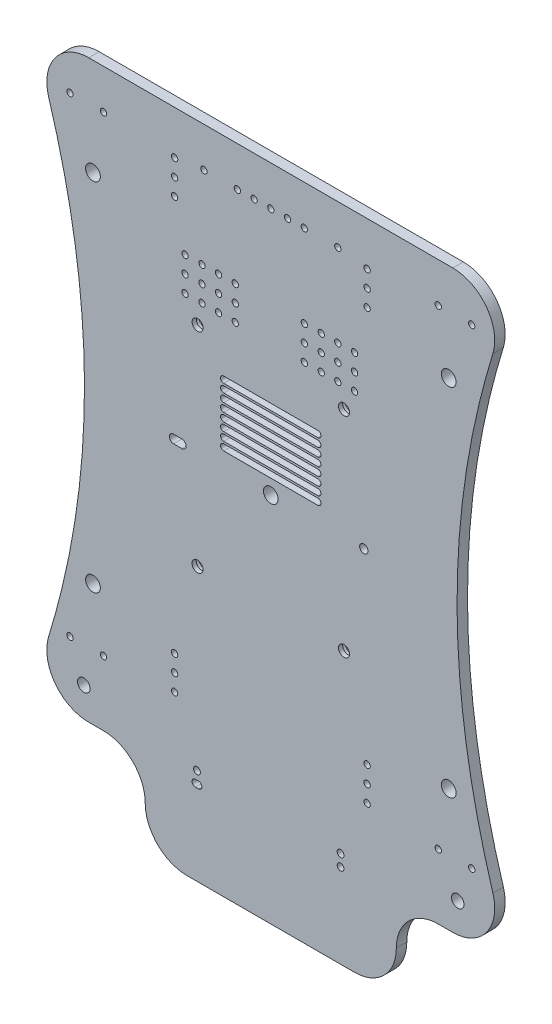
SolidWorks part; units mm, degrees
material "尼龙 101"
ref_plane "前视基准面" through (0, 0, 0) normal (0, 0, 1) x (1, 0, 0)
ref_plane "上视基准面" through (0, 0, 0) normal (0, 1, 0) x (1, 0, 0)
ref_plane "右视基准面" through (0, 0, 0) normal (1, 0, 0) x (0, 0, -1)
other "质心 (COM)"
sketch "草图1" plane through (0, 0, 0) normal (0, 0, 1) x (1, 0, 0)
  line L1 (219.5668, -321.513) -> (-113.5668, -321.513)
  line L2 (219.5668, -321.513) -> (219.5668, 86.513)
  line L3 (219.5668, 86.513) -> (-113.5668, 86.513)
  line L4 (-113.5668, -321.513) -> (-113.5668, 86.513)
  line L5 (53, 86.513) -> (53, -321.513) construction
  line L6 (219.5668, -117.5) -> (-113.5668, -117.5) construction
  point P0 (53, -117.5)
extrude "凸台-拉伸1" add sketch "草图1" along normal blind 5
sketch "草图2" plane through (0, 0, 0) normal (0, 0, -1) x (-1, 0, 0)
  line L0 (-16.9368, -260.7382) -> (-18.4087, -260.7382) construction
  line L1 (-16.9368, -262.3514) -> (-18.4087, -262.3514)
  line L2 (-16.9368, -259.125) -> (-18.4087, -259.125)
  line L3 (-6.5227, -123.5) -> (-10.4914, -123.5) construction
  line L4 (-6.5227, -125.5059) -> (-10.4914, -125.5059)
  line L5 (-6.5227, -121.4941) -> (-10.4914, -121.4941)
  circle A0 centre (-148.989, -4.9924) radius 1.5134
  circle A1 centre (-133, -5) radius 1.5134
  circle A2 centre (26.9975, -4.9986) radius 1.5134
  circle A3 centre (42.9864, -5.0062) radius 1.5134
  circle A4 centre (-149, -230) radius 1.5134
  circle A5 centre (-133, -230) radius 1.5134
  circle A6 centre (27, -230) radius 1.5134
  circle A7 centre (42.9864, -230) radius 1.5134
  circle A8 centre (-99, -212) radius 1.5134
  circle A9 centre (-99, -220) radius 1.5134
  circle A10 centre (-99, -228) radius 1.5134
  circle A11 centre (-7, -228) radius 1.5134
  circle A12 centre (-7, -212) radius 1.5134
  circle A13 centre (-7, -220) radius 1.5134
  circle A16 centre (-99, -6.872) radius 1.5134
  circle A17 centre (-99, -14.872) radius 1.5134
  circle A18 centre (-99, -22.872) radius 1.5134
  circle A19 centre (-7, -22.872) radius 1.5134
  circle A20 centre (-7, -6.872) radius 1.5134
  circle A21 centre (-7, -14.872) radius 1.5134
  circle A44 centre (-36, -60.5) radius 1.5134
  circle A45 centre (-12, -44.5) radius 1.5134
  circle A46 centre (-77.0909, -52.5) radius 1.5134
  circle A47 centre (-69, -60.5) radius 1.5134
  circle A48 centre (-93, -44.5) radius 1.5134
  circle A49 centre (-36, -44.5) radius 1.5134
  circle A50 centre (-93, -60.5) radius 1.5134
  circle A51 centre (-20.0909, -44.5) radius 1.5134
  circle A52 centre (-12, -60.5) radius 1.5134
  circle A53 centre (-28, -52.5) radius 1.5134
  circle A54 centre (-69, -44.5) radius 1.5134
  circle A55 centre (-85, -60.5) radius 1.5134
  circle A56 centre (-36, -52.5) radius 1.5134
  circle A57 centre (-20.0909, -52.5) radius 1.5134
  circle A58 centre (-69, -52.5) radius 1.5134
  circle A59 centre (-93, -52.5) radius 1.5134
  circle A60 centre (-85, -44.5) radius 1.5134
  circle A61 centre (-12, -52.5) radius 1.5134
  circle A62 centre (-28, -44.5) radius 1.5134
  circle A63 centre (-20.0909, -60.5) radius 1.5134
  circle A64 centre (-77.0909, -44.5) radius 1.5134
  circle A65 centre (-28, -60.5) radius 1.5134
  circle A66 centre (-85, -52.5) radius 1.5134
  circle A67 centre (-77.0909, -60.5) radius 1.5134
  circle A68 centre (-85, -5) radius 1.5134
  circle A69 centre (-69, -5) radius 1.5134
  circle A70 centre (-61, -5) radius 1.5134
  circle A71 centre (-53, -5) radius 1.5134
  circle A72 centre (-45, -5) radius 1.5134
  circle A73 centre (-37, -5) radius 1.5134
  circle A74 centre (-21, -5) radius 1.5134
  circle A75 centre (32.0139, -32.4785) radius 3.5256
  circle A76 centre (-138, -32.5) radius 3.5256
  circle A77 centre (32.0139, -202.6407) radius 3.5256
  circle A78 centre (-138, -202.5) radius 3.5256
  circle A79 centre (-17.9993, -70.5429) radius 2.6429
  circle A80 centre (-87.9571, -70.5) radius 2.6429
  circle A81 centre (-87.9571, -170.5) radius 2.6429
  circle A82 centre (-17.9571, -170.5) radius 2.6429
  circle A83 centre (-52.9571, -123.5) radius 3.5
  circle A84 centre (-86.322, -255.1502) radius 1.6383
  circle A85 centre (-86.322, -260.7382) radius 1.6066
  circle A86 centre (-17.6728, -255.1502) radius 1.6383
  arc A91 (-16.9368, -262.3514) -> (-16.9368, -259.125) centre (-16.9368, -260.7382) ccw
  arc A92 (-18.4087, -259.125) -> (-18.4087, -262.3514) centre (-18.4087, -260.7382) ccw
  circle A93 centre (-52.9571, -123.5) radius 44.45 construction
  circle A95 centre (-97.4071, -123.5) radius 1.9844
  arc A96 (-6.5227, -125.5059) -> (-6.5227, -121.4941) centre (-6.5227, -123.5) ccw
  arc A97 (-10.4914, -121.4941) -> (-10.4914, -125.5059) centre (-10.4914, -123.5) ccw
  point P70 (-17.6728, -260.7382)
  point P80 (-8.5071, -123.5)
extrude "切除-拉伸1" cut sketch "草图2" against normal through all
sketch "草图3" plane through (0, 0, 0) normal (0, 0, -1) x (-1, 0, 0)
  circle A0 centre (-17.9571, -170.5) radius 5
  circle A1 centre (-87.9571, -170.5) radius 5
  circle A2 centre (-17.9993, -70.5429) radius 5
  circle A3 centre (-87.9571, -70.5429) radius 5
extrude "切除-拉伸2" cut sketch "草图3" against normal blind 3
sketch "草图4" plane through (0, 0, 5) normal (0, 0, 1) x (1, 0, 0)
  line L9 (167.9571, -261) -> (112.9571, -261)
  line L10 (112.9571, -261) -> (112.9571, -301)
  line L11 (112.9571, -301) -> (-7.0429, -301)
  line L12 (-7.0429, -301) -> (-7.0429, -261)
  line L13 (-7.0429, -261) -> (-62.0429, -261)
  line L16 (-62.0429, 14) -> (167.9571, 14)
  line L18 (167.9571, -261) -> (-62.0429, 14) construction
  line L19 (-62.0429, -261) -> (167.9571, 14) construction
  line L20 (52.9571, 14) -> (52.9571, -301) construction
  spline S0 degree 2 poles (167.9571, -261) (116.0066, -123.3546) (167.9571, 14) knots 0 0 0 1 1 1
  spline S1 degree 2 poles (-62.0429, -261) (-10.0925, -123.3546) (-62.0429, 14) knots 0 0 0 1 1 1
  dimension "D1" = 55
  dimension "D2" = 120
  dimension "D3" = 40
  dimension "D4" = 275
extrude "切除-拉伸3" cut sketch "草图4" against normal through all flip side to cut
fillet "圆角1" radius 20 4 edges at (167.9571, 14, 2.5) (-62.0429, 14, 2.5) (-62.0429, -261, 2.5) (167.9571, -261, 2.5)
fillet "圆角2" radius 20 4 edges at (-7.0429, -301, 2.5) (112.9571, -301, 2.5) (-7.0429, -261, 2.5) (112.9571, -261, 2.5)
sketch "草图5" plane through (0, 0, 0) normal (0, 0, -1) x (-1, 0, 0)
  line L0 (-52.9571, -123.5) -> (-52.9571, -48.5) construction
  line L1 (-75.4571, -114.9826) -> (-30.4571, -114.9826) construction
  line L2 (-75.4571, -113.4826) -> (-30.4571, -113.4826)
  line L3 (-75.4571, -116.4826) -> (-30.4571, -116.4826)
  line L4 (-75.4571, -110.9826) -> (-30.4571, -110.9826) construction
  line L5 (-75.4571, -109.4826) -> (-30.4571, -109.4826)
  line L6 (-75.4571, -112.4826) -> (-30.4571, -112.4826)
  line L7 (-75.4571, -106.9826) -> (-30.4571, -106.9826) construction
  line L8 (-75.4571, -105.4826) -> (-30.4571, -105.4826)
  line L9 (-75.4571, -108.4826) -> (-30.4571, -108.4826)
  line L10 (-75.4571, -102.9826) -> (-30.4571, -102.9826) construction
  line L11 (-75.4571, -101.4826) -> (-30.4571, -101.4826)
  line L12 (-75.4571, -104.4826) -> (-30.4571, -104.4826)
  line L13 (-75.4571, -98.9826) -> (-30.4571, -98.9826) construction
  line L14 (-75.4571, -97.4826) -> (-30.4571, -97.4826)
  line L15 (-75.4571, -100.4826) -> (-30.4571, -100.4826)
  line L16 (-75.4571, -94.9826) -> (-30.4571, -94.9826) construction
  line L17 (-75.4571, -93.4826) -> (-30.4571, -93.4826)
  line L18 (-75.4571, -96.4826) -> (-30.4571, -96.4826)
  line L19 (-75.4571, -90.9826) -> (-30.4571, -90.9826) construction
  line L20 (-75.4571, -89.4826) -> (-30.4571, -89.4826)
  line L21 (-75.4571, -92.4826) -> (-30.4571, -92.4826)
  line L22 (-75.4571, -86.9826) -> (-30.4571, -86.9826) construction
  line L23 (-75.4571, -85.4826) -> (-30.4571, -85.4826)
  line L24 (-75.4571, -88.4826) -> (-30.4571, -88.4826)
  arc A0 (-75.4571, -113.4826) -> (-75.4571, -116.4826) centre (-75.4571, -114.9826) ccw
  arc A1 (-30.4571, -116.4826) -> (-30.4571, -113.4826) centre (-30.4571, -114.9826) ccw
  arc A2 (-75.4571, -109.4826) -> (-75.4571, -112.4826) centre (-75.4571, -110.9826) ccw
  arc A3 (-30.4571, -112.4826) -> (-30.4571, -109.4826) centre (-30.4571, -110.9826) ccw
  arc A4 (-75.4571, -105.4826) -> (-75.4571, -108.4826) centre (-75.4571, -106.9826) ccw
  arc A5 (-30.4571, -108.4826) -> (-30.4571, -105.4826) centre (-30.4571, -106.9826) ccw
  arc A6 (-75.4571, -101.4826) -> (-75.4571, -104.4826) centre (-75.4571, -102.9826) ccw
  arc A7 (-30.4571, -104.4826) -> (-30.4571, -101.4826) centre (-30.4571, -102.9826) ccw
  arc A8 (-75.4571, -97.4826) -> (-75.4571, -100.4826) centre (-75.4571, -98.9826) ccw
  arc A9 (-30.4571, -100.4826) -> (-30.4571, -97.4826) centre (-30.4571, -98.9826) ccw
  arc A10 (-75.4571, -93.4826) -> (-75.4571, -96.4826) centre (-75.4571, -94.9826) ccw
  arc A11 (-30.4571, -96.4826) -> (-30.4571, -93.4826) centre (-30.4571, -94.9826) ccw
  arc A12 (-75.4571, -89.4826) -> (-75.4571, -92.4826) centre (-75.4571, -90.9826) ccw
  arc A13 (-30.4571, -92.4826) -> (-30.4571, -89.4826) centre (-30.4571, -90.9826) ccw
  arc A14 (-75.4571, -85.4826) -> (-75.4571, -88.4826) centre (-75.4571, -86.9826) ccw
  arc A15 (-30.4571, -88.4826) -> (-30.4571, -85.4826) centre (-30.4571, -86.9826) ccw
  point P5 (-52.9571, -114.9826)
  point P14 (-52.9571, -110.9826)
  point P21 (-52.9571, -106.9826)
  point P28 (-52.9571, -102.9826)
  point P35 (-52.9571, -98.9826)
  point P42 (-52.9571, -94.9826)
  point P49 (-52.9571, -90.9826)
  point P56 (-52.9571, -86.9826)
  dimension "D1" = 8
extrude "切除-拉伸4" cut sketch "草图5" against normal through all
sketch "草图6" plane through (0, 0, 5) normal (0, 0, 1) x (1, 0, 0)
  circle A0 centre (-36.3943, -246.7998) radius 3
  circle A1 centre (142.3084, -246.7998) radius 3
extrude "切除-拉伸5" cut sketch "草图6" against normal through all
